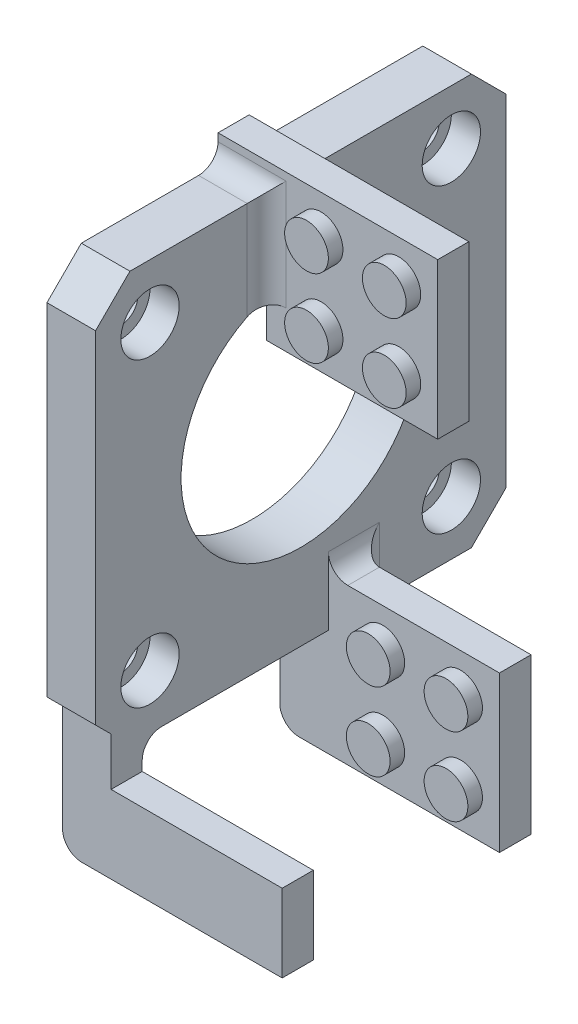
SolidWorks part; units mm, degrees
ref_plane "Front Plane" through (0, 0, 0) normal (0, 0, 1) x (1, 0, 0)
ref_plane "Top Plane" through (0, 0, 0) normal (0, 1, 0) x (1, 0, 0)
ref_plane "Right Plane" through (0, 0, 0) normal (1, 0, 0) x (0, 0, -1)
sketch "Sketch4" plane through (-14.6, 0, 0) normal (1, 0, 0) x (0, 0, -1)
  line L2 (11.2546, -49.194) -> (11.2546, 14.806) construction
  line L4 (-1.5454, -49.194) -> (-1.5454, -33.194) construction
  line L5 (17.6046, -33.194) -> (17.6046, -49.194) construction
  line L6 (11.2546, -49.194) -> (11.2546, 14.806) construction
  line L7 (11.2546, -49.194) -> (11.2546, 14.806) construction
  line L8 (-6.3454, 0.4704) -> (-6.3454, -34.6585)
  line L9 (-6.3454, -34.6585) -> (-2.8099, -38.194)
  line L10 (-2.8099, -38.194) -> (32.3191, -38.194)
  line L11 (32.3191, -38.194) -> (35.8546, -34.6585)
  line L12 (35.8546, -34.6585) -> (35.8546, 0.4704)
  line L13 (35.8546, 0.4704) -> (32.3191, 4.006)
  line L14 (32.3191, 4.006) -> (-2.8099, 4.006)
  line L15 (-2.8099, 4.006) -> (-6.3454, 0.4704)
  line L16 (-6.3454, 0.4704) -> (-6.3454, -34.6585)
  line L17 (-6.3454, -34.6585) -> (-2.8099, -38.194)
  line L18 (-2.8099, -38.194) -> (32.3191, -38.194)
  line L19 (32.3191, -38.194) -> (35.8546, -34.6585)
  line L20 (35.8546, -34.6585) -> (35.8546, 0.4704)
  line L21 (35.8546, 0.4704) -> (32.3191, 4.006)
  line L22 (32.3191, 4.006) -> (-2.8099, 4.006)
  line L23 (-2.8099, 4.006) -> (-6.3454, 0.4704)
  line L24 (-1.5454, -49.194) -> (-1.5454, -33.194) construction
  line L25 (17.6046, -33.194) -> (17.6046, -49.194) construction
  line L26 (11.2546, -47.594) -> (11.2546, -42.794) construction
  line L27 (11.2546, -39.594) -> (11.2546, -34.794) construction
  line L28 (11.2546, 0.406) -> (11.2546, 5.206) construction
  line L29 (11.2546, -7.594) -> (11.2546, -2.794) construction
  line L30 (11.2546, -47.594) -> (11.2546, -42.794) construction
  line L31 (11.2546, -39.594) -> (11.2546, -34.794) construction
  line L32 (11.2546, 0.406) -> (11.2546, 5.206) construction
  line L33 (11.2546, -7.594) -> (11.2546, -2.794) construction
  line L34 (-1.5454, -38.194) -> (-1.5454, -49.194)
  line L35 (20.8546, -49.194) -> (17.6046, -49.194)
  line L36 (20.8546, -49.194) -> (20.8546, -33.194)
  line L37 (20.8546, -33.194) -> (17.6046, -33.194)
  line L38 (17.6046, -49.194) -> (17.6046, -33.194)
  line L39 (20.8546, -49.194) -> (17.6046, -33.194) construction
  line L40 (20.8546, -33.194) -> (17.6046, -49.194) construction
  line L41 (-1.5454, -49.194) -> (-4.7454, -49.194)
  line L42 (-4.7454, -49.194) -> (-4.7454, -36.2585)
  line L43 (11.2546, -41.194) -> (-4.7454, -41.194)
  line L44 (11.2546, -9.194) -> (14.4546, -9.194)
  line L45 (14.4546, -9.194) -> (14.4546, 6.806)
  line L46 (14.4546, 6.806) -> (11.2546, 6.806)
  line L47 (11.2546, 6.806) -> (11.2546, -9.194)
  line L48 (11.2546, -2.794) -> (11.2546, 0.406) construction
  line L49 (11.2546, -2.794) -> (11.2546, 0.406)
  circle A0 centre (14.7546, -17.094) radius 12.3
  circle A1 centre (14.7546, -17.094) radius 12
  circle A2 centre (14.7546, -17.094) radius 12 construction
  arc A3 (30.2546, -0.334) -> (29.2407, -0.8459) centre (30.2546, -1.594) ccw
  arc A4 (31.2685, -0.8459) -> (30.2546, -0.334) centre (30.2546, -1.594) ccw
  arc A5 (29.6767, -2.9891) -> (30.8324, -2.9891) centre (30.2546, -1.594) ccw
  arc A6 (30.2546, -0.334) -> (29.2407, -0.8459) centre (30.2546, -1.594) ccw construction
  arc A7 (31.2685, -0.8459) -> (30.2546, -0.334) centre (30.2546, -1.594) ccw construction
  arc A8 (29.6767, -2.9891) -> (30.8324, -2.9891) centre (30.2546, -1.594) ccw construction
  arc A9 (30.2546, -31.334) -> (29.2407, -31.8459) centre (30.2546, -32.594) ccw
  arc A10 (31.2685, -31.8459) -> (30.2546, -31.334) centre (30.2546, -32.594) ccw
  arc A11 (29.6767, -33.9891) -> (30.8324, -33.9891) centre (30.2546, -32.594) ccw
  arc A12 (30.2546, -31.334) -> (29.2407, -31.8459) centre (30.2546, -32.594) ccw construction
  arc A13 (31.2685, -31.8459) -> (30.2546, -31.334) centre (30.2546, -32.594) ccw construction
  arc A14 (29.6767, -33.9891) -> (30.8324, -33.9891) centre (30.2546, -32.594) ccw construction
  arc A15 (-0.7454, -0.334) -> (-1.7593, -0.8459) centre (-0.7454, -1.594) ccw
  arc A16 (0.2685, -0.8459) -> (-0.7454, -0.334) centre (-0.7454, -1.594) ccw
  arc A17 (-1.3233, -2.9891) -> (-0.1676, -2.9891) centre (-0.7454, -1.594) ccw
  arc A18 (-0.7454, -0.334) -> (-1.7593, -0.8459) centre (-0.7454, -1.594) ccw construction
  arc A19 (0.2685, -0.8459) -> (-0.7454, -0.334) centre (-0.7454, -1.594) ccw construction
  arc A20 (-1.3233, -2.9891) -> (-0.1676, -2.9891) centre (-0.7454, -1.594) ccw construction
  arc A21 (-0.7454, -31.334) -> (-1.7593, -31.8459) centre (-0.7454, -32.594) ccw
  arc A22 (0.2685, -31.8459) -> (-0.7454, -31.334) centre (-0.7454, -32.594) ccw
  arc A23 (-1.3233, -33.9891) -> (-0.1676, -33.9891) centre (-0.7454, -32.594) ccw
  arc A24 (-0.7454, -31.334) -> (-1.7593, -31.8459) centre (-0.7454, -32.594) ccw construction
  arc A25 (0.2685, -31.8459) -> (-0.7454, -31.334) centre (-0.7454, -32.594) ccw construction
  arc A26 (-1.3233, -33.9891) -> (-0.1676, -33.9891) centre (-0.7454, -32.594) ccw construction
  circle A27 centre (-0.7454, -32.594) radius 1.75
  circle A28 centre (-0.7454, -32.594) radius 3
  circle A29 centre (-0.7454, -1.594) radius 1.75
  circle A30 centre (-0.7454, -1.594) radius 3
  circle A31 centre (30.2546, -1.594) radius 1.75
  circle A32 centre (30.2546, -1.594) radius 3
  circle A33 centre (30.2546, -32.594) radius 1.75
  circle A34 centre (30.2546, -32.594) radius 3
  spline S2 degree 6 poles (1416.109, -1445.2831) (36.5495, 19.5258) (42.2492, 9.3255) (23.5656, 4.5699) (26.025, -3.8798) (30.1217, -4.2099) (31.4012, -2.4681) (31.4587, -2.3722) (31.507, -2.2715) (31.5454, -2.1669) (31.5736, -2.0598) (31.6095, -1.8395) (31.6167, -1.7262) (31.6125, -1.6129) (31.5971, -1.501) (31.5705, -1.3919) (30.9149, 0.4612) (27.361, 1.0487) (23.2159, -6.052) (40.0913, -18.1944) (65.1794, -26.2102) (1503.4217, 1352.3912) knots -4.213254 -4.213254 -4.213254 -4.213254 -4.213254 -4.213254 -4.213254 0.240234 0.240234 0.240234 0.240234 0.240234 0.482752 0.482752 0.482752 0.482752 0.482752 0.732681 0.732681 0.732681 0.732681 0.732681 4.898115 4.898115 4.898115 4.898115 4.898115 4.898115 4.898115 weights 1 1 1 1 1 1 1 1 1 1 1 1 1 1 1 1 1 1 1 1 1 1 only from (30.8324, -2.9891) to (31.2685, -0.8459)
  spline S3 degree 6 poles (-1441.994, 1353.3548) (-4.7582, -26.2184) (20.4368, -18.1909) (37.2912, -6.0484) (33.147, 1.0485) (29.5942, 0.4609) (28.9387, -1.3919) (28.9121, -1.501) (28.8966, -1.6129) (28.8925, -1.7262) (28.8996, -1.8395) (28.9356, -2.0598) (28.9638, -2.1669) (29.0022, -2.2715) (29.0504, -2.3722) (29.108, -2.4681) (30.3875, -4.2099) (34.4842, -3.8798) (36.9436, 4.57) (18.2592, 9.3243) (23.9798, 19.5389) (-1355.77, -1445.1389) knots -3.897393 -3.897393 -3.897393 -3.897393 -3.897393 -3.897393 -3.897393 0.267319 0.267319 0.267319 0.267319 0.267319 0.517248 0.517248 0.517248 0.517248 0.517248 0.759766 0.759766 0.759766 0.759766 0.759766 5.213238 5.213238 5.213238 5.213238 5.213238 5.213238 5.213238 weights 1 1 1 1 1 1 1 1 1 1 1 1 1 1 1 1 1 1 1 1 1 1 only from (29.2407, -0.8459) to (29.6767, -2.9891)
  spline S4 degree 6 poles (30.8324, -2.9891) (30.9316, -2.937) (31.0259, -2.8761) (31.1143, -2.8071) (31.1958, -2.7305) (31.2697, -2.6471) (31.4012, -2.4681) (31.4587, -2.3722) (31.507, -2.2715) (31.5454, -2.1669) (31.5736, -2.0598) (31.6095, -1.8395) (31.6167, -1.7262) (31.6125, -1.6129) (31.5971, -1.501) (31.5705, -1.3919) (31.5044, -1.205) (31.4689, -1.1255) (31.4272, -1.0492) (31.3796, -0.9769) (31.3265, -0.9089) (31.2685, -0.8459) knots 0 0 0 0 0 0 0 0.240234 0.240234 0.240234 0.240234 0.240234 0.482752 0.482752 0.482752 0.482752 0.482752 0.732681 0.732681 0.732681 0.732681 0.732681 0.928164 0.928164 0.928164 0.928164 0.928164 0.928164 0.928164 weights 1 1 1 1 1 1 1 1 1 1 1 1 1 1 1 1 1 1 1 1 1 1 construction
  spline S5 degree 6 poles (29.2407, -0.8459) (29.1827, -0.9089) (29.1296, -0.9768) (29.082, -1.0492) (29.0403, -1.1255) (29.0048, -1.205) (28.9387, -1.3919) (28.9121, -1.501) (28.8966, -1.6129) (28.8925, -1.7262) (28.8996, -1.8395) (28.9356, -2.0598) (28.9638, -2.1669) (29.0022, -2.2715) (29.0504, -2.3722) (29.108, -2.4681) (29.2395, -2.6471) (29.3134, -2.7305) (29.3949, -2.8071) (29.4833, -2.8761) (29.5776, -2.937) (29.6767, -2.9891) knots 0.071831 0.071831 0.071831 0.071831 0.071831 0.071831 0.071831 0.267319 0.267319 0.267319 0.267319 0.267319 0.517248 0.517248 0.517248 0.517248 0.517248 0.759766 0.759766 0.759766 0.759766 0.759766 1 1 1 1 1 1 1 weights 1 1 1 1 1 1 1 1 1 1 1 1 1 1 1 1 1 1 1 1 1 1 construction
  spline S6 degree 6 poles (1416.109, -1476.2818) (36.5495, -11.4742) (42.2492, -21.6745) (23.5656, -26.4301) (26.025, -34.8798) (30.1217, -35.2099) (31.4012, -33.4681) (31.4587, -33.3722) (31.507, -33.2715) (31.5454, -33.1669) (31.5736, -33.0598) (31.6095, -32.8395) (31.6167, -32.7262) (31.6125, -32.6129) (31.5971, -32.501) (31.5705, -32.3919) (30.9149, -30.5388) (27.361, -29.9513) (23.2159, -37.052) (40.0913, -49.1944) (65.1794, -57.2102) (1503.4217, 1321.3909) knots -4.213254 -4.213254 -4.213254 -4.213254 -4.213254 -4.213254 -4.213254 0.240234 0.240234 0.240234 0.240234 0.240234 0.482752 0.482752 0.482752 0.482752 0.482752 0.732681 0.732681 0.732681 0.732681 0.732681 4.898115 4.898115 4.898115 4.898115 4.898115 4.898115 4.898115 weights 1 1 1 1 1 1 1 1 1 1 1 1 1 1 1 1 1 1 1 1 1 1 only from (30.8324, -33.9891) to (31.2685, -31.8459)
  spline S7 degree 6 poles (-1441.994, 1322.3549) (-4.7582, -57.2183) (20.4368, -49.1909) (37.2912, -37.0484) (33.147, -29.9515) (29.5942, -30.5391) (28.9387, -32.3919) (28.9121, -32.501) (28.8966, -32.6129) (28.8925, -32.7262) (28.8996, -32.8395) (28.9356, -33.0598) (28.9638, -33.1669) (29.0022, -33.2715) (29.0504, -33.3722) (29.108, -33.4681) (30.3875, -35.2099) (34.4842, -34.8798) (36.9436, -26.43) (18.2592, -21.6757) (23.9798, -11.4613) (-1355.77, -1476.1345) knots -3.897393 -3.897393 -3.897393 -3.897393 -3.897393 -3.897393 -3.897393 0.267319 0.267319 0.267319 0.267319 0.267319 0.517248 0.517248 0.517248 0.517248 0.517248 0.759766 0.759766 0.759766 0.759766 0.759766 5.213238 5.213238 5.213238 5.213238 5.213238 5.213238 5.213238 weights 1 1 1 1 1 1 1 1 1 1 1 1 1 1 1 1 1 1 1 1 1 1 only from (29.2407, -31.8459) to (29.6767, -33.9891)
  spline S8 degree 6 poles (30.8324, -33.9891) (30.9316, -33.937) (31.0259, -33.8761) (31.1143, -33.8071) (31.1958, -33.7305) (31.2697, -33.6471) (31.4012, -33.4681) (31.4587, -33.3722) (31.507, -33.2715) (31.5454, -33.1669) (31.5736, -33.0598) (31.6095, -32.8395) (31.6167, -32.7262) (31.6125, -32.6129) (31.5971, -32.501) (31.5705, -32.3919) (31.5044, -32.205) (31.4689, -32.1255) (31.4272, -32.0492) (31.3796, -31.9769) (31.3265, -31.9089) (31.2685, -31.8459) knots 0 0 0 0 0 0 0 0.240234 0.240234 0.240234 0.240234 0.240234 0.482752 0.482752 0.482752 0.482752 0.482752 0.732681 0.732681 0.732681 0.732681 0.732681 0.928164 0.928164 0.928164 0.928164 0.928164 0.928164 0.928164 weights 1 1 1 1 1 1 1 1 1 1 1 1 1 1 1 1 1 1 1 1 1 1 construction
  spline S9 degree 6 poles (29.2407, -31.8459) (29.1827, -31.9089) (29.1296, -31.9768) (29.082, -32.0492) (29.0403, -32.1255) (29.0048, -32.205) (28.9387, -32.3919) (28.9121, -32.501) (28.8966, -32.6129) (28.8925, -32.7262) (28.8996, -32.8395) (28.9356, -33.0598) (28.9638, -33.1669) (29.0022, -33.2715) (29.0504, -33.3722) (29.108, -33.4681) (29.2395, -33.6471) (29.3134, -33.7305) (29.3949, -33.8071) (29.4833, -33.8761) (29.5776, -33.937) (29.6767, -33.9891) knots 0.071831 0.071831 0.071831 0.071831 0.071831 0.071831 0.071831 0.267319 0.267319 0.267319 0.267319 0.267319 0.517248 0.517248 0.517248 0.517248 0.517248 0.759766 0.759766 0.759766 0.759766 0.759766 1 1 1 1 1 1 1 weights 1 1 1 1 1 1 1 1 1 1 1 1 1 1 1 1 1 1 1 1 1 1 construction
  spline S10 degree 6 poles (1385.0993, -1445.2713) (5.5496, 19.5258) (11.2491, 9.3255) (-7.4344, 4.5699) (-4.975, -3.8798) (-0.8783, -4.2099) (0.4012, -2.4681) (0.4587, -2.3722) (0.507, -2.2715) (0.5454, -2.1669) (0.5736, -2.0598) (0.6095, -1.8395) (0.6167, -1.7262) (0.6125, -1.6129) (0.5971, -1.501) (0.5705, -1.3919) (-0.0851, 0.4612) (-3.639, 1.0487) (-7.784, -6.0519) (9.0909, -18.1941) (34.1787, -26.21) (1472.3697, 1352.3412) knots -4.213248 -4.213248 -4.213248 -4.213248 -4.213248 -4.213248 -4.213248 0.240234 0.240234 0.240234 0.240234 0.240234 0.482752 0.482752 0.482752 0.482752 0.482752 0.732681 0.732681 0.732681 0.732681 0.732681 4.89809 4.89809 4.89809 4.89809 4.89809 4.89809 4.89809 weights 1 1 1 1 1 1 1 1 1 1 1 1 1 1 1 1 1 1 1 1 1 1 only from (-0.1676, -2.9891) to (0.2685, -0.8459)
  spline S11 degree 6 poles (-1472.9924, 1353.3551) (-35.7582, -26.2184) (-10.5632, -18.1909) (6.2912, -6.0484) (2.147, 1.0485) (-1.4058, 0.4609) (-2.0613, -1.3919) (-2.0879, -1.501) (-2.1034, -1.6129) (-2.1075, -1.7262) (-2.1004, -1.8395) (-2.0644, -2.0598) (-2.0362, -2.1669) (-1.9978, -2.2715) (-1.9496, -2.3722) (-1.892, -2.4681) (-0.6125, -4.2099) (3.4842, -3.8798) (5.9436, 4.57) (-12.7408, 9.3243) (-7.0201, 19.5389) (-1386.7727, -1445.1389) knots -3.897393 -3.897393 -3.897393 -3.897393 -3.897393 -3.897393 -3.897393 0.267319 0.267319 0.267319 0.267319 0.267319 0.517248 0.517248 0.517248 0.517248 0.517248 0.759766 0.759766 0.759766 0.759766 0.759766 5.213238 5.213238 5.213238 5.213238 5.213238 5.213238 5.213238 weights 1 1 1 1 1 1 1 1 1 1 1 1 1 1 1 1 1 1 1 1 1 1 only from (-1.7593, -0.8459) to (-1.3233, -2.9891)
  spline S12 degree 6 poles (-0.1676, -2.9891) (-0.0684, -2.937) (0.0259, -2.8761) (0.1143, -2.8071) (0.1958, -2.7305) (0.2697, -2.6471) (0.4012, -2.4681) (0.4587, -2.3722) (0.507, -2.2715) (0.5454, -2.1669) (0.5736, -2.0598) (0.6095, -1.8395) (0.6167, -1.7262) (0.6125, -1.6129) (0.5971, -1.501) (0.5705, -1.3919) (0.5044, -1.205) (0.4689, -1.1255) (0.4272, -1.0492) (0.3796, -0.9769) (0.3265, -0.9089) (0.2685, -0.8459) knots 0 0 0 0 0 0 0 0.240234 0.240234 0.240234 0.240234 0.240234 0.482752 0.482752 0.482752 0.482752 0.482752 0.732681 0.732681 0.732681 0.732681 0.732681 0.928164 0.928164 0.928164 0.928164 0.928164 0.928164 0.928164 weights 1 1 1 1 1 1 1 1 1 1 1 1 1 1 1 1 1 1 1 1 1 1 construction
  spline S13 degree 6 poles (-1.7593, -0.8459) (-1.8173, -0.9089) (-1.8704, -0.9768) (-1.918, -1.0492) (-1.9597, -1.1255) (-1.9952, -1.205) (-2.0613, -1.3919) (-2.0879, -1.501) (-2.1034, -1.6129) (-2.1075, -1.7262) (-2.1004, -1.8395) (-2.0644, -2.0598) (-2.0362, -2.1669) (-1.9978, -2.2715) (-1.9496, -2.3722) (-1.892, -2.4681) (-1.7605, -2.6471) (-1.6866, -2.7305) (-1.6051, -2.8071) (-1.5167, -2.8761) (-1.4224, -2.937) (-1.3233, -2.9891) knots 0.071831 0.071831 0.071831 0.071831 0.071831 0.071831 0.071831 0.267319 0.267319 0.267319 0.267319 0.267319 0.517248 0.517248 0.517248 0.517248 0.517248 0.759766 0.759766 0.759766 0.759766 0.759766 1 1 1 1 1 1 1 weights 1 1 1 1 1 1 1 1 1 1 1 1 1 1 1 1 1 1 1 1 1 1 construction
  spline S14 degree 6 poles (1385.0999, -1476.27) (5.5495, -11.4743) (11.2491, -21.6745) (-7.4344, -26.4301) (-4.975, -34.8798) (-0.8783, -35.2099) (0.4012, -33.4681) (0.4587, -33.3722) (0.507, -33.2715) (0.5454, -33.1669) (0.5736, -33.0598) (0.6095, -32.8395) (0.6167, -32.7262) (0.6125, -32.6129) (0.5971, -32.501) (0.5705, -32.3919) (-0.0851, -30.5388) (-3.639, -29.9513) (-7.784, -37.0519) (9.0909, -49.1941) (34.1787, -57.21) (1472.3697, 1321.341) knots -4.213248 -4.213248 -4.213248 -4.213248 -4.213248 -4.213248 -4.213248 0.240234 0.240234 0.240234 0.240234 0.240234 0.482752 0.482752 0.482752 0.482752 0.482752 0.732681 0.732681 0.732681 0.732681 0.732681 4.89809 4.89809 4.89809 4.89809 4.89809 4.89809 4.89809 weights 1 1 1 1 1 1 1 1 1 1 1 1 1 1 1 1 1 1 1 1 1 1 only from (-0.1676, -33.9891) to (0.2685, -31.8459)
  spline S15 degree 6 poles (-1472.9924, 1322.3549) (-35.7582, -57.2183) (-10.5632, -49.1909) (6.2912, -37.0484) (2.147, -29.9515) (-1.4058, -30.5391) (-2.0613, -32.3919) (-2.0879, -32.501) (-2.1034, -32.6129) (-2.1075, -32.7262) (-2.1004, -32.8395) (-2.0644, -33.0598) (-2.0362, -33.1669) (-1.9978, -33.2715) (-1.9496, -33.3722) (-1.892, -33.4681) (-0.6125, -35.2099) (3.4842, -34.8798) (5.9436, -26.43) (-12.7408, -21.6757) (-7.0201, -11.4613) (-1386.7727, -1476.1345) knots -3.897393 -3.897393 -3.897393 -3.897393 -3.897393 -3.897393 -3.897393 0.267319 0.267319 0.267319 0.267319 0.267319 0.517248 0.517248 0.517248 0.517248 0.517248 0.759766 0.759766 0.759766 0.759766 0.759766 5.213238 5.213238 5.213238 5.213238 5.213238 5.213238 5.213238 weights 1 1 1 1 1 1 1 1 1 1 1 1 1 1 1 1 1 1 1 1 1 1 only from (-1.7593, -31.8459) to (-1.3233, -33.9891)
  spline S16 degree 6 poles (-0.1676, -33.9891) (-0.0684, -33.937) (0.0259, -33.8761) (0.1143, -33.8071) (0.1958, -33.7305) (0.2697, -33.6471) (0.4012, -33.4681) (0.4587, -33.3722) (0.507, -33.2715) (0.5454, -33.1669) (0.5736, -33.0598) (0.6095, -32.8395) (0.6167, -32.7262) (0.6125, -32.6129) (0.5971, -32.501) (0.5705, -32.3919) (0.5044, -32.205) (0.4689, -32.1255) (0.4272, -32.0492) (0.3796, -31.9769) (0.3265, -31.9089) (0.2685, -31.8459) knots 0 0 0 0 0 0 0 0.240234 0.240234 0.240234 0.240234 0.240234 0.482752 0.482752 0.482752 0.482752 0.482752 0.732681 0.732681 0.732681 0.732681 0.732681 0.928164 0.928164 0.928164 0.928164 0.928164 0.928164 0.928164 weights 1 1 1 1 1 1 1 1 1 1 1 1 1 1 1 1 1 1 1 1 1 1 construction
  spline S17 degree 6 poles (-1.7593, -31.8459) (-1.8173, -31.9089) (-1.8704, -31.9768) (-1.918, -32.0492) (-1.9597, -32.1255) (-1.9952, -32.205) (-2.0613, -32.3919) (-2.0879, -32.501) (-2.1034, -32.6129) (-2.1075, -32.7262) (-2.1004, -32.8395) (-2.0644, -33.0598) (-2.0362, -33.1669) (-1.9978, -33.2715) (-1.9496, -33.3722) (-1.892, -33.4681) (-1.7605, -33.6471) (-1.6866, -33.7305) (-1.6051, -33.8071) (-1.5167, -33.8761) (-1.4224, -33.937) (-1.3233, -33.9891) knots 0.071831 0.071831 0.071831 0.071831 0.071831 0.071831 0.071831 0.267319 0.267319 0.267319 0.267319 0.267319 0.517248 0.517248 0.517248 0.517248 0.517248 0.759766 0.759766 0.759766 0.759766 0.759766 1 1 1 1 1 1 1 weights 1 1 1 1 1 1 1 1 1 1 1 1 1 1 1 1 1 1 1 1 1 1 construction
  point P67 (19.2296, -41.194)
  point P81 (11.2546, -1.194)
  point P82 (14.4546, -1.194)
  dimension "D8" = 6
  dimension "D9" = 3.5
  dimension "D12" = 3.2
  dimension "D10" = 9.6
  dimension "D11" = 3.2
  dimension "D13" = 16
  dimension "D14" = 3.2
  dimension "D1" = 0
  dimension "D2" = 0
  dimension "D3" = 0
  dimension "D4" = 0
  dimension "D5" = 0
  dimension "D6" = 0
  dimension "D7" = 0.3
extrude "Boss-Extrude1" add sketch "Sketch4" along normal blind 5 contours A0 L47 L17 L18 L38 L37 L36 L45 A34 A32 A30 A28 | A34 A33 | A28 A27 | A30 A29 | A32 A31 | L46 L47 L22 L45 | L34 L43 L42 L41 | L38 L35 L36 | L43 L34 L17 L42 | L38 L36 L37 | A0 L45 L22 L47 region at (-14.6, 1.8162, 4.1556) region at (-14.6, -39.3438, 3.3013) region at (-14.6, 5.406, -12.8546) region at (-14.6, -0.4871, -12.8397) region at (-14.6, -45.194, 3.1454) region at (-14.6, -35.694, -19.2296) region at (-14.6, -43.694, -19.2296) region at (-14.6, -32.594, 3.6606) region at (-14.6, -1.594, 3.6606) region at (-14.6, -1.594, -27.3394) region at (-14.6, -32.594, -27.3394)
extrude "Boss-Extrude2" add sketch "Sketch4<3>" along normal up to surface (17.6 mm away) from surface contours L38 L35 L36 | L38 L36 L37 | L34 L43 L42 L41 | A0 L45 L22 L47 | L47 L44 L45 | L45 A0 L47 | L46 L47 L22 L45 region at (-14.6, 5.406, -12.8546) region at (-14.6, -0.4871, -12.8397) region at (-14.6, -45.194, 3.1454) region at (-14.6, -5.132, -12.8432) region at (-14.6, -35.694, -19.2296) region at (-14.6, -43.694, -19.2296) region at (-14.6, -7.2353, -12.8898) starting at face at (-9.6, -22.3448, -12.4527)
sketch "Sketch4<3>" plane through (-14.6, 0, 0) normal (1, 0, 0) x (0, 0, -1) same geometry as "Sketch4"
sketch "Sketch5" plane through (0, 0, -17.6046) normal (0, 0, 1) x (1, 0, 0)
  circle A0 centre (-4, -5.194) radius 2.4 construction
  circle A1 centre (4, -5.194) radius 2.4 construction
  circle A2 centre (4, 2.806) radius 2.4 construction
  circle A3 centre (-4, 2.806) radius 2.4 construction
  circle A4 centre (4, -45.194) radius 2.4 construction
  circle A5 centre (-4, -45.194) radius 2.4 construction
  circle A6 centre (-4, -37.194) radius 2.4 construction
  circle A7 centre (4, -37.194) radius 2.4 construction
  circle A8 centre (-4, -5.194) radius 2.4 construction
  circle A9 centre (4, -5.194) radius 2.4 construction
  circle A10 centre (4, 2.806) radius 2.4 construction
  circle A11 centre (-4, 2.806) radius 2.4 construction
  circle A12 centre (4, -45.194) radius 2.4 construction
  circle A13 centre (-4, -45.194) radius 2.4 construction
  circle A14 centre (-4, -37.194) radius 2.4 construction
  circle A15 centre (4, -37.194) radius 2.4 construction
  circle A16 centre (-4, -45.194) radius 2.55
  circle A17 centre (-4, -45.194) radius 2.25
  circle A18 centre (4, -45.194) radius 2.25
  circle A19 centre (4, -45.194) radius 2.55
  circle A20 centre (-4, -37.194) radius 2.25
  circle A21 centre (4, -37.194) radius 2.25
  circle A22 centre (-4, 2.806) radius 2.25
  circle A23 centre (4, 2.806) radius 2.25
  circle A24 centre (4, -5.194) radius 2.25
  circle A25 centre (-4, -5.194) radius 2.25
  dimension "D1" = 0.15
  dimension "D2" = 0.15
extrude "Boss-Extrude3" add sketch "Sketch5" along normal blind 1.5 contours A17 | A18 | A21 | A20 region at (-4, -45.194, -17.6046) region at (4, -45.194, -17.6046) region at (-4, -37.194, -17.6046) region at (4, -37.194, -17.6046)
extrude "Boss-Extrude4" add sketch "Sketch5<4>" along normal blind 1.5 from surface contours A22 | A25 | A23 | A24 region at (-4, 2.806, -17.6046) region at (4, 2.806, -17.6046) region at (4, -5.194, -17.6046) region at (-4, -5.194, -17.6046) starting at face at (-6, -0.2953, -11.2546)
sketch "Sketch5<4>" plane through (0, 0, -17.6046) normal (0, 0, 1) x (1, 0, 0) same geometry as "Sketch5"
extrude "Cut-Extrude1" cut sketch "Sketch5<5>" along normal blind 1.7 from surface contours A19 | A16 starting at face at (-5.4, -42.8607, 1.5454)
sketch "Sketch5<5>" plane through (0, 0, -17.6046) normal (0, 0, 1) x (1, 0, 0) same geometry as "Sketch5"
fillet "Fillet1" radius 2 10 edges at (-12.1, -38.194, 1.5454) (-12.1, 4.006, -11.2546) (-9.6, -0.6483, -11.2546) (-14.6, -49.194, 3.1454) (-14.6, -49.194, -19.2296) (-9.6, -33.194, -19.2296) (-12.1, -38.194, -20.8546) (-9.6, -35.694, -20.8546) (-12.1, 4.006, -14.4546) (-9.6, -0.3959, -14.4546)
extrude "Cut-Extrude2" cut sketch "Sketch4<4>" against normal blind 3 from surface contours A28 A27 | A30 A29 | A32 A31 | A34 A33 region at (-14.6, -32.594, 3.6606) region at (-14.6, -1.594, 3.6606) region at (-14.6, -1.594, -27.3394) region at (-14.6, -32.594, -27.3394) starting at face at (-9.6, -30.844, 0.7454)
sketch "Sketch4<4>" plane through (-14.6, 0, 0) normal (1, 0, 0) x (0, 0, -1) same geometry as "Sketch4"
